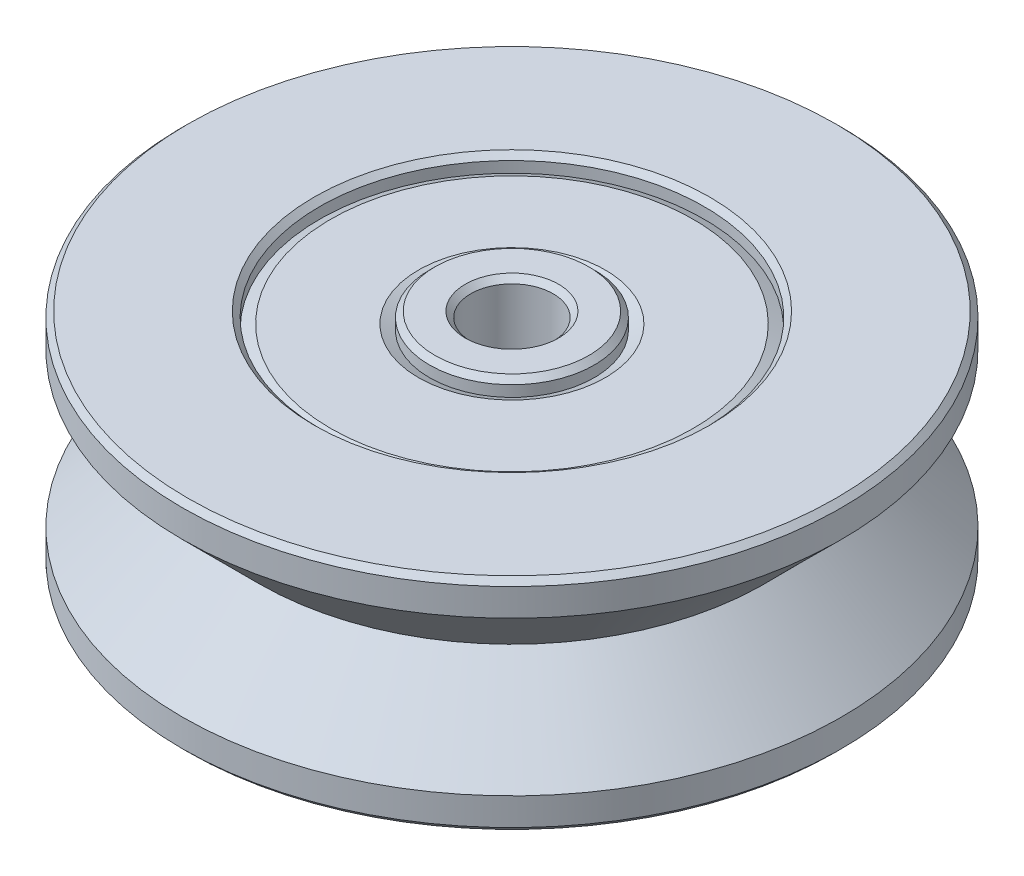
SolidWorks part; units mm, degrees
ref_plane "Front Plane" through (0, 0, 0) normal (0, 0, 1) x (1, 0, 0)
ref_plane "Top Plane" through (0, 0, 0) normal (0, 1, 0) x (1, 0, 0)
ref_plane "Right Plane" through (0, 0, 0) normal (1, 0, 0) x (0, 0, -1)
sketch "Sketch1" plane through (0, 0, 0) normal (1, 0, 0) x (0, 0, -1)
  line L0 (6, 1.4) -> (4.6, 0)
  line L1 (0, 2) -> (6, 2)
  line L2 (0, 2) -> (0, -2) construction
  line L3 (0, -2) -> (6, -2)
  line L4 (6, 2) -> (6, -2)
  line L5 (4.6, 0) -> (6, -1.4)
  line L6 (4.6, 0) -> (0, 0) construction
  line L7 (0.75, 2) -> (0.75, -2)
  dimension "D1" = 4
  dimension "D2" = 6
  dimension "D3" = 1.4
  dimension "D4" = 2.8
  dimension "D5" = 1.5
revolve "Revolve1" add sketch "Sketch1" angle 360 about L2 region at (0, 0, -3.1528)
sketch "Sketch3" plane through (0, 0, 0) normal (1, 0, 0) x (0, 0, -1)
  line L0 (6, 2) -> (6, -2) construction
  line L1 (0.75, 2) -> (0.75, -2) construction
  line L2 (0, 2) -> (6, 2) construction
  line L3 (6, 2) -> (6, -2) construction
  line L4 (0.75, 2) -> (0.75, -2)
  line L5 (0, 2) -> (6, 2) construction
  line L6 (1.5, 2) -> (3.5, 2)
  line L7 (1.5, 2) -> (1.5, 1.7)
  line L8 (1.5, 1.7) -> (1.7, 1.8)
  line L9 (1.7, 1.8) -> (3.3, 1.8)
  line L10 (3.3, 1.8) -> (3.5, 1.7)
  line L11 (3.5, 1.7) -> (3.5, 2)
  line L12 (4.6, 0) -> (6, -1.4) construction
  line L13 (6, 1.4) -> (4.6, 0) construction
  line L14 (0, 2) -> (0, -2) construction
  line L15 (4.6, 0) -> (6, -1.4)
  line L16 (6, 1.4) -> (4.6, 0) construction
  line L17 (0, 2) -> (0, -2) construction
  line L18 (1.5, 1.7) -> (3.5, 1.7) construction
  line L19 (2.5, 1.7) -> (2.5, 2) construction
  dimension "D1" = 2.5
  dimension "D2" = 0.2
  dimension "D3" = 0.75
  dimension "D4" = 0.1
  dimension "D5" = 0.2
revolve "Cut-Revolve2" cut sketch "Sketch3" angle 360 about L17 region at (0, 1.8937, -2.5)
mirror "Mirror1" about plane through (0, 0, 0) normal (0, 1, 0) of "Cut-Revolve2"
chamfer "Chamfer1" distance 0.1 angle 45 8 edges at (0, -2, 3.5) (0, 2, 3.5) (0, -2, 6) (0, 2, 6) (0, -2, 1.5) (0, 2, 1.5) (0, 2, 0.75) (0, -2, 0.75)
